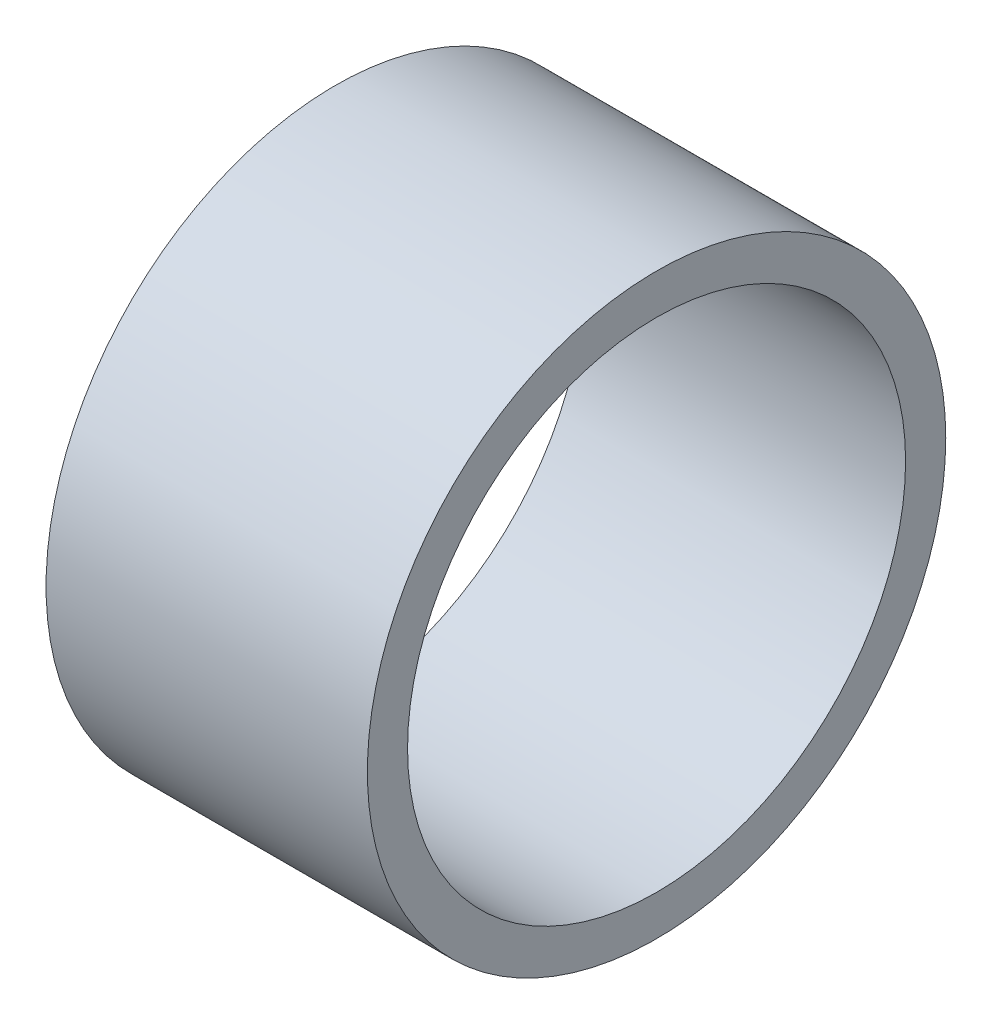
SolidWorks part; units mm, degrees
material "AISI 1020"
ref_plane "Front Plane" through (0, 0, 0) normal (0, 0, 1) x (1, 0, 0)
ref_plane "Top Plane" through (0, 0, 0) normal (0, 1, 0) x (1, 0, 0)
ref_plane "Right Plane" through (0, 0, 0) normal (1, 0, 0) x (0, 0, -1)
sketch "Sketch1" plane through (0, 0, 0) normal (1, 0, 0) x (0, 0, -1)
  circle A0 centre (0, 0) radius 22.86
  circle A1 centre (0, 0) radius 19.685
  dimension "D1" = 45.72
  dimension "D2" = 3.175
extrude "Boss-Extrude1" add sketch "Sketch1" along normal mid plane 25.4
